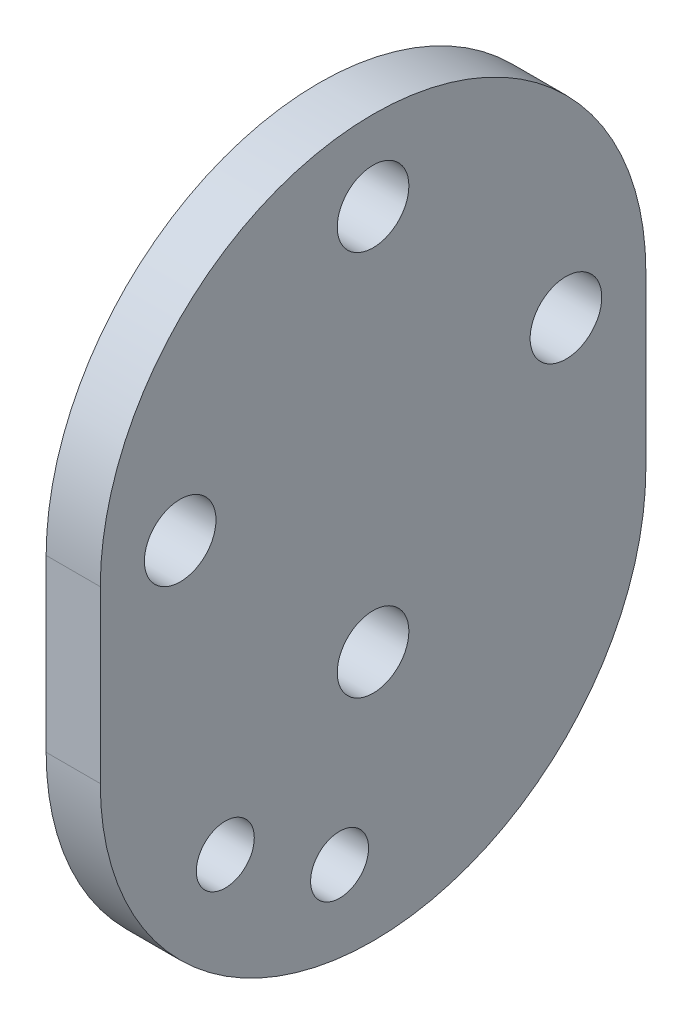
SolidWorks part; units mm, degrees
ref_plane "Front" through (0, 0, 0) normal (0, 0, 1) x (1, 0, 0)
ref_plane "Top" through (0, 0, 0) normal (0, 1, 0) x (1, 0, 0)
ref_plane "Right" through (0, 0, 0) normal (1, 0, 0) x (0, 0, -1)
sketch "Sketch2" plane through (0, 0, 0) normal (1, 0, 0) x (0, 0, -1)
  line L0 (0, -5) -> (0, 5) construction
  line L1 (-16, -5) -> (-16, 5)
  line L2 (16, -5) -> (16, 5)
  line L3 (0, -6.3137) -> (7.4244, -19.1732)
  line L4 (41.4915, -10.0987) -> (41.4915, -0.0987) construction
  line L7 (25.4915, -10.0987) -> (25.4915, -0.0987)
  line L8 (0, -6.3137) -> (-15.946, -6.3137)
  line L9 (0, -6.3137) -> (-7.9856, -13.0144)
  line L10 (-7.9856, -13.0144) -> (0, -6.3137)
  line L11 (-1.7395, -16.1792) -> (0, -6.3137)
  line L12 (57.4915, -10.0987) -> (57.4915, -0.0987)
  line L13 (41.4915, -10.0987) -> (25.4915, -10.0987)
  line L14 (41.4915, -10.0987) -> (38.7131, -25.8556)
  line L15 (38.7131, -25.8556) -> (41.4915, -10.0987)
  line L16 (41.4915, -10.0987) -> (29.2348, -20.3833)
  arc A0 (-16, -5) -> (16, -5) centre (0, -5) ccw
  arc A1 (16, 5) -> (-16, 5) centre (0, 5) ccw
  circle A2 centre (0, 5) radius 11.3137
  circle A3 centre (0, 16.3137) radius 2.1
  circle A4 centre (0, -6.3137) radius 2.1
  circle A5 centre (11.3137, 5) radius 2.1
  circle A6 centre (-11.3137, 5) radius 2.1
  circle A7 centre (0, -5) radius 11.3137
  circle A18 centre (-7.9856, -13.0144) radius 1.7
  circle A19 centre (-1.7395, -16.1792) radius 1.7
  arc A20 (25.4915, -10.0987) -> (57.4915, -10.0987) centre (41.4915, -10.0987) ccw
  arc A21 (57.4915, -0.0987) -> (25.4915, -0.0987) centre (41.4915, -0.0987) ccw
  circle A22 centre (41.4915, -0.0987) radius 11.3137
  circle A23 centre (41.4915, -10.0987) radius 11.3137
  circle A24 centre (39.5269, -21.2405) radius 1.7
  circle A25 centre (32.8247, -17.371) radius 1.7
  circle A26 centre (41.4915, 11.215) radius 2.1
  circle A27 centre (30.1778, -0.0987) radius 2.1
  circle A28 centre (41.4915, -11.4124) radius 2.1
  circle A29 centre (52.8052, -0.0987) radius 2.1
  point P2 (0, 0)
  point P24 (41.4915, -5.0987)
  dimension "D1" = 16
  dimension "D2" = 22.6274
  dimension "D3" = 22.6274
  dimension "D4" = 40
  dimension "D6" = 120
  dimension "D7" = 80
  dimension "D5" = 40
  dimension "D8" = 40
extrude "Boss-Extrude1" add sketch "Sketch2" along normal blind 3.175 contours A28 L14 A24 A23 A22 | A28 L16 A25 A23 A24 L14 | A28 A22 L13 A23 A25 L16 | A28 L13 A22 | A22 A23 L13 | A28 A22 A23 L13 | A25 A23 L13 A20 L16 | A29 A22 A23 A24 L15 A20 L12 A21 L7 L13 A27 A26 | A25 L16 A20 L15 A24 A23 | A29 A22 A26 A27 A23 region at (0, -5.0987, -26.0195) region at (0, -14.5801, -28.6268) region at (0, -8.4969, -32.2309) region at (0, -12.6207, -34.1745) region at (0, -22.0009, -34.6197) region at (0, -4.8233, -41.5321) region at (0, -10.4961, -38.3598) region at (0, 4.1693, -41.4915) region at (0, -14.5772, -46.6842) region at (0, -16.6308, -37.7118)
